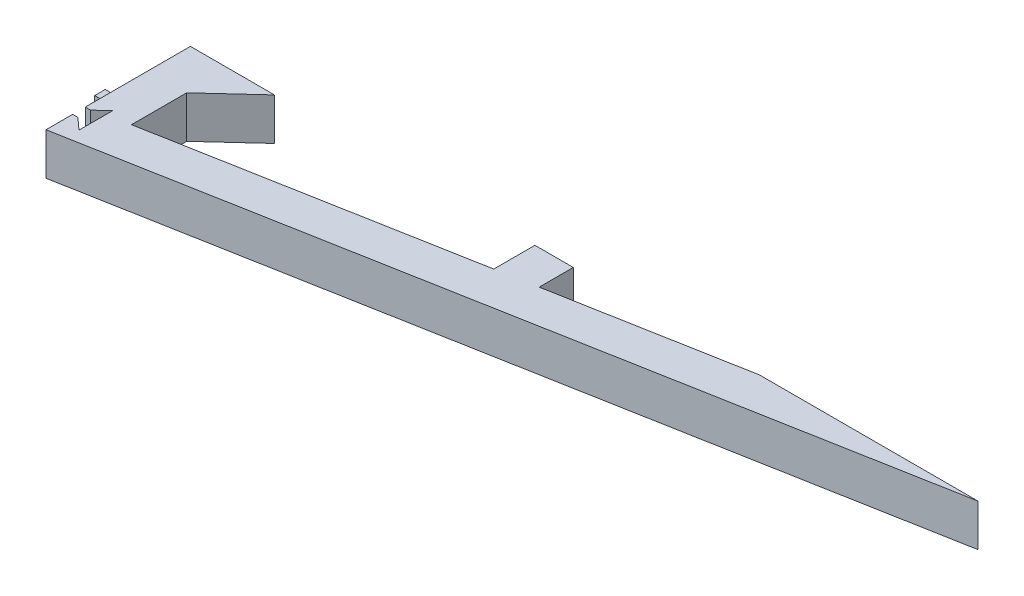
SolidWorks part; units mm, degrees
ref_plane "Přední rovina" through (0, 0, 0) normal (0, 0, 1) x (1, 0, 0)
ref_plane "Horní rovina" through (0, 0, 0) normal (0, 1, 0) x (1, 0, 0)
ref_plane "Pravá rovina" through (0, 0, 0) normal (1, 0, 0) x (0, 0, -1)
sketch "Skica1" plane through (0, 0, 0) normal (0, 1, 0) x (1, 0, 0)
  line L0 (0, 0) -> (0, -27.4721)
  line L1 (0, -27.4721) -> (149.85, 0.0008)
  line L7 (65.55, -7.8294) -> (7.3, -18.5088)
  line L8 (7.3, -18.5088) -> (7.3, 0)
  line L9 (7.3, 0) -> (0, 0)
  line L15 (65.55, -7.8294) -> (65.55, 0)
  line L16 (65.55, 0) -> (72.85, 0)
  line L17 (72.85, 0) -> (72.85, -6.4911)
  line L18 (72.85, -6.4911) -> (108.2597, 0.0008)
  line L19 (108.2597, 0.0008) -> (149.85, 0.0008)
  dimension "D1" = 27.4721
  dimension "D2" = 7.3
  dimension "D3" = 149.85
  dimension "D4" = 7.3
  dimension "D5" = 7.5
  dimension "D6" = 79.611
  dimension "D7" = 77
  dimension "D8" = 7.5
extrude "Přidat vysunutím1" add sketch "Skica1" along normal blind 8
sketch "Skica2" plane through (0, 8, 0) normal (0, 1, 0) x (1, 0, 0)
  line L6 (0, -20) -> (1, -20)
  line L7 (0, 0) -> (0, -27.4721) construction
  line L8 (1, -20) -> (3.2, -18)
  line L9 (3.2, -18) -> (3.2, -24.4)
  line L10 (3.2, -24.4) -> (1, -22.4)
  line L11 (1, -22.4) -> (0, -22.4)
  line L12 (0, -22.4) -> (0, -20)
  line L13 (7.3, 0) -> (0, 0) construction
  dimension "D1" = 1
  dimension "D2" = 1
  dimension "D3" = 3.2
  dimension "6,8" = 6.4
  dimension "2,8" = 2.4
  dimension "D4" = 2
  dimension "4" = 18
extrude "Odebrat vysunutím1" cut sketch "Skica2" against normal through all
sketch "Skica3" plane through (0, 0, 0) normal (-1, 0, 0) x (0, 0, 1)
  line L0 (0, 8) -> (0, 0) construction
  line L5 (12.2, 5) -> (14.2, 5)
  line L6 (12.2, 5) -> (12.2, 3)
  line L7 (12.2, 3) -> (14.2, 3)
  line L8 (14.2, 5) -> (14.2, 3)
  line L14 (0, 8) -> (20, 8) construction
  dimension "D1" = 12.2
  dimension "D3" = 2
  dimension "D4" = 2
  dimension "D9" = 3
extrude "Přidat vysunutím2" add sketch "Skica3" along normal blind 4
sketch "Skica5" plane through (0, 8, 0) normal (0, 1, 0) x (1, 0, 0)
  line L11 (0, 0) -> (16, 0)
  line L12 (0, 0) -> (0, -8)
  line L13 (0, -8) -> (16, -8)
  line L14 (16, 0) -> (16, -8)
  dimension "D1" = 16
  dimension "D2" = 8
extrude "Přidat vysunutím4" add sketch "Skica5" against normal blind 8
sketch "Skica7" plane through (0, 0, 0) normal (0, -1, 0) x (1, 0, 0)
  line L3 (7.3, 8) -> (16, 8)
  line L4 (16, 8) -> (16, 0)
  line L5 (16, 0) -> (7.3, 8)
extrude "Odebrat vysunutím3" cut sketch "Skica7" against normal through all
sketch "Skica8" plane through (0, 0, 0) normal (0, 0, -1) x (-1, 0, 0)
  line L0 (0, 8) -> (0, 0) construction
  line L1 (-16, 8) -> (0, 8) construction
  line L2 (-72.85, 0) -> (-65.55, 0) construction
  line L3 (-65.55, 8) -> (-65.55, 0) construction
  circle A0 centre (-3.65, 4) radius 2.2
  circle A1 centre (-69.2, 4) radius 2.2
  dimension "D1" = 4.4
  dimension "D2" = 4.4
  dimension "D3" = 3.65
  dimension "D4" = 4
  dimension "D5" = 4
  dimension "D6" = 3.65
extrude "Odebrat vysunutím4" cut sketch "Skica8" against normal blind 2.4
sketch "Skica9" plane through (0, 0, 2.4) normal (0, 0, -1) x (-1, 0, 0)
  circle A0 centre (-69.2, 4) radius 1.85
  circle A1 centre (-3.65, 4) radius 1.85
  dimension "D1" = 3.7
  dimension "D2" = 3.7
extrude "Odebrat vysunutím5" cut sketch "Skica9" against normal blind 7
